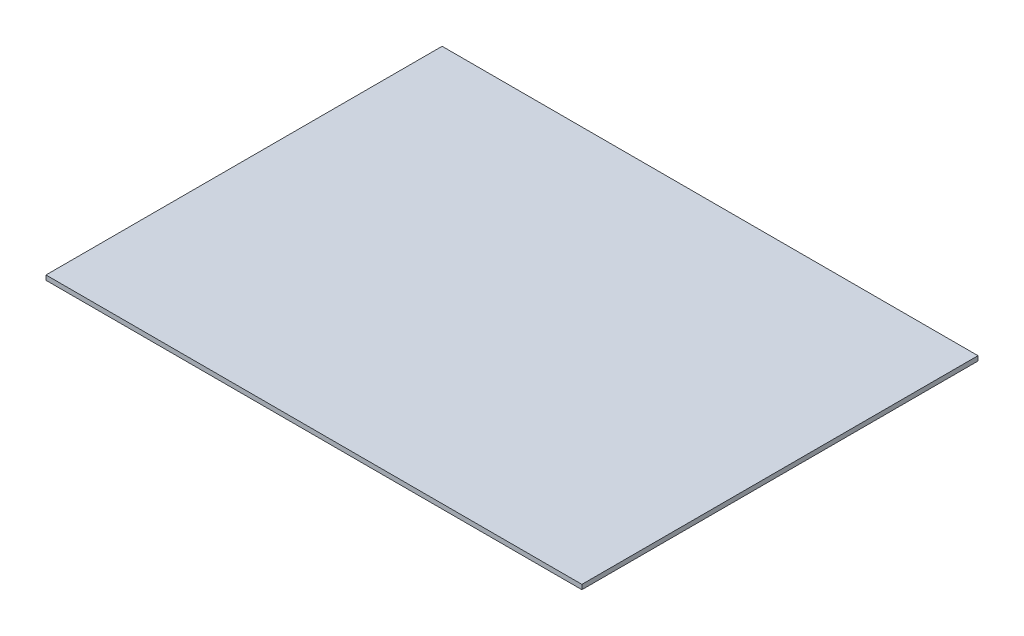
SolidWorks part; units mm, degrees
ref_plane "Спереди" through (0, 0, 0) normal (0, 0, 1) x (1, 0, 0)
ref_plane "Сверху" through (0, 0, 0) normal (0, 1, 0) x (1, 0, 0)
ref_plane "Справа" through (0, 0, 0) normal (1, 0, 0) x (0, 0, -1)
sketch "Эскиз1" plane through (0, 0, 0) normal (0, 1, 0) x (1, 0, 0)
  line L1 (-57.5, -42.5) -> (57.5, -42.5)
  line L2 (-57.5, -42.5) -> (-57.5, 42.5)
  line L3 (-57.5, 42.5) -> (57.5, 42.5)
  line L4 (57.5, -42.5) -> (57.5, 42.5)
  line L5 (-57.5, -42.5) -> (57.5, 42.5) construction
  line L6 (-57.5, 42.5) -> (57.5, -42.5) construction
  point P0 (0, 0)
  dimension "D1" = 85
  dimension "D2" = 115
extrude "Бобышка-Вытянуть1" add sketch "Эскиз1" along normal blind 1
